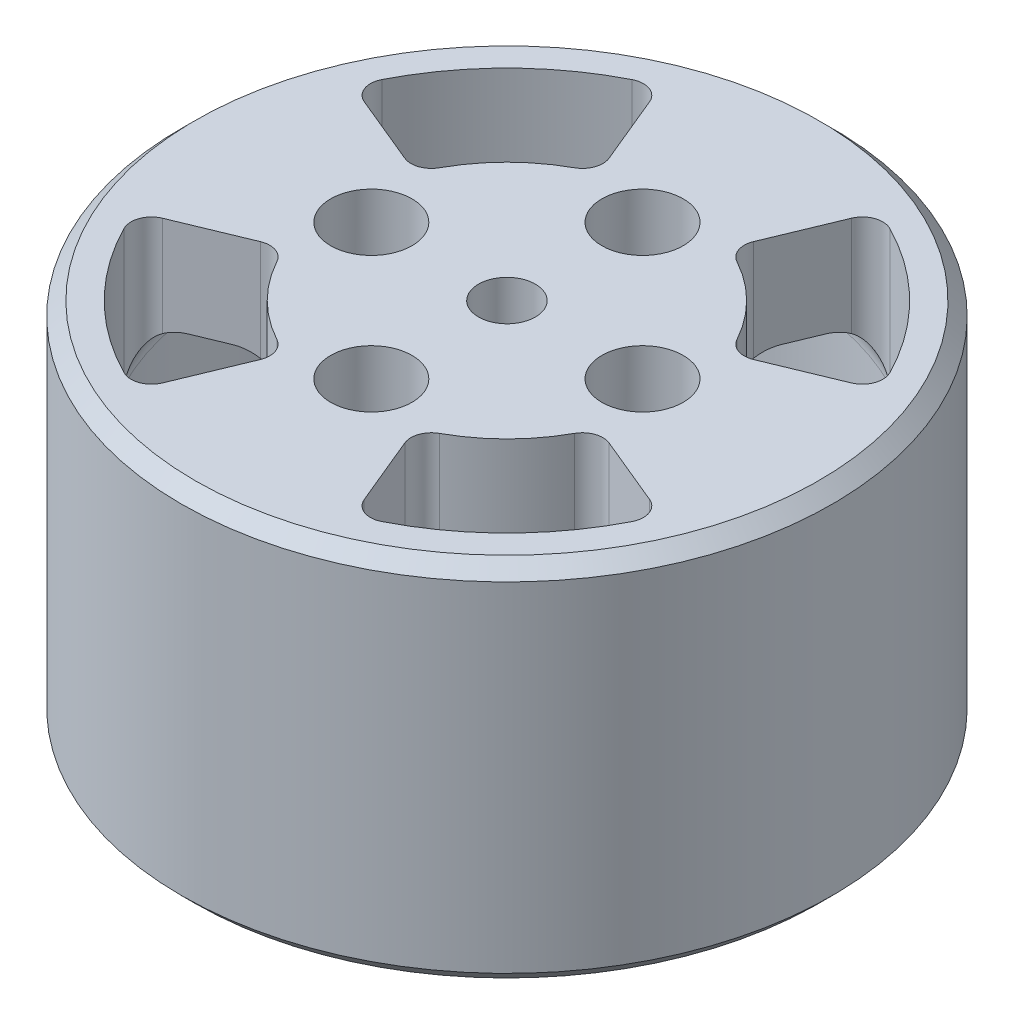
SolidWorks part; units mm, degrees
ref_plane "前视基准面" through (0, 0, 0) normal (0, 0, 1) x (1, 0, 0)
ref_plane "上视基准面" through (0, 0, 0) normal (0, 1, 0) x (1, 0, 0)
ref_plane "右视基准面" through (0, 0, 0) normal (1, 0, 0) x (0, 0, -1)
sketch "草图1" plane through (0, 0, 0) normal (0, 1, 0) x (1, 0, 0)
  circle A0 centre (0, 0) radius 24
  dimension "D1" = 48
extrude "凸台-拉伸1" add sketch "草图1" along normal blind 27
sketch "草图2" plane through (0, 0, 0) normal (0, -1, 0) x (1, 0, 0)
  circle A0 centre (0, 0) radius 21
  dimension "D1" = 42
extrude "切除-拉伸1" cut sketch "草图2" against normal offset from surface (17 mm away) 10 up to face at (0, 27, 24)
sketch "草图3" plane through (0, 27, 0) normal (0, 1, 0) x (1, 0, 0)
  circle A0 centre (0, 0) radius 10 construction
  circle A1 centre (0, 10) radius 1.65
  circle A2 centre (10, 0) radius 1.65
  circle A3 centre (0, -10) radius 1.65
  circle A4 centre (-10, 0) radius 1.65
  dimension "D1" = 20
  dimension "D2" = 3.3
extrude "切除-拉伸2" cut sketch "草图3" against normal up to next
sketch "草图4" plane through (0, 27, 0) normal (0, 1, 0) x (1, 0, 0)
  circle A0 centre (0, 10) radius 3
  circle A1 centre (10, 0) radius 3
  circle A2 centre (0, -10) radius 3
  circle A3 centre (-10, 0) radius 3
  dimension "D1" = 6
extrude "切除-拉伸3" cut sketch "草图4" against normal blind 5
sketch "草图5" plane through (0, 27, 0) normal (0, 1, 0) x (1, 0, 0)
  circle A0 centre (0, 0) radius 2.1
  dimension "D1" = 4.2
extrude "切除-拉伸4" cut sketch "草图5" against normal up to next
sketch "草图6" plane through (0, 17, 0) normal (0, -1, 0) x (1, 0, 0)
  line L0 (0, 0) -> (-4.7835, 11.5485) construction
  line L1 (-4.7835, 11.5485) -> (-8.0364, 19.4015)
  line L2 (0, 0) -> (-11.5485, 4.7835) construction
  line L3 (-11.5485, 4.7835) -> (-19.4015, 8.0364)
  line L4 (0, 0) -> (-12.5, 0) construction
  line L5 (0, 0) -> (0, 12.5) construction
  circle A0 centre (0, 0) radius 21 construction
  circle A1 centre (0, 0) radius 21 construction
  circle A2 centre (0, 0) radius 12.5 construction
  arc A3 (-19.4015, 8.0364) -> (-8.0364, 19.4015) centre (0, 0) cw
  arc A4 (-11.5485, 4.7835) -> (-4.7835, 11.5485) centre (0, 0) cw
  dimension "D1" = 25
  dimension "D2" = 22.5
  dimension "D3" = 22.5
extrude "切除-拉伸5" cut sketch "草图6" against normal up to next
sketch "草图7" plane through (0, 0, 0) normal (0, 0, 1) x (1, 0, 0)
  line L0 (0, 0) -> (0, 27) construction
  line L1 (3, 27) -> (-3, 27) construction
pattern_circular "阵列(圆周)1" count 4 over 360 about axis through (0, 0, 0) along (0, 1, 0) of "切除-拉伸5"
sketch "草图8" plane through (0, 17, 0) normal (0, -1, 0) x (1, 0, 0)
  circle A1 centre (0, 0) radius 12.5
  circle A2 centre (0, 0) radius 21
extrude "切除-拉伸6" cut sketch "草图8" against normal blind 3
fillet "圆角1" radius 3 8 edges at (0, 20, -21) (0, 20, -12.5) (12.5, 20, 0) (21, 20, 0) (-12.5, 20, 0) (-21, 20, 0) (0, 20, 12.5) (0, 20, 21)
fillet "圆角2" radius 1.5 16 edges at (-4.7835, 22, 11.5485) (-11.5485, 22, 4.7835) (-19.4015, 22, 8.0364) (-8.0364, 22, 19.4015) (-11.5485, 22, -4.7835) (-4.7835, 22, -11.5485) (-8.0364, 22, -19.4015) (-19.4015, 22, -8.0364) (4.7835, 22, -11.5485) (11.5485, 22, -4.7835) (19.4015, 22, -8.0364) (8.0364, 22, -19.4015) (11.5485, 22, 4.7835) (4.7835, 22, 11.5485) (8.0364, 22, 19.4015) (19.4015, 22, 8.0364)
sketch "草图9" plane through (0, 22, 0) normal (0, 1, 0) x (1, 0, 0)
  line L1 (-13, 2.5055) -> (-11.65, 2.5055)
  line L2 (-13, 2.5055) -> (-13, -2.5055)
  line L3 (-13, -2.5055) -> (-11.65, -2.5055)
  line L4 (-11.65, 2.5055) -> (-11.65, -2.5055)
  line L5 (-8.35, -2.5055) -> (-7, -2.5055)
  line L6 (-8.35, -2.5055) -> (-8.35, 2.5055)
  line L7 (-8.35, 2.5055) -> (-7, 2.5055)
  line L8 (-7, -2.5055) -> (-7, 2.5055)
  circle A0 centre (-10, 0) radius 3 construction
  circle A2 centre (-10, 0) radius 1.65 construction
  circle A3 centre (-10, 0) radius 3 construction
extrude "凸台-拉伸2" add sketch "草图9" along normal blind 0.2
pattern_circular "阵列(圆周)2" count 4 over 360 about axis through (0, 0, 0) along (0, 1, 0) of "凸台-拉伸2"
chamfer "倒角1" distance 1 angle 45 2 edges at (0, 27, 24) (0, 0, 24)
